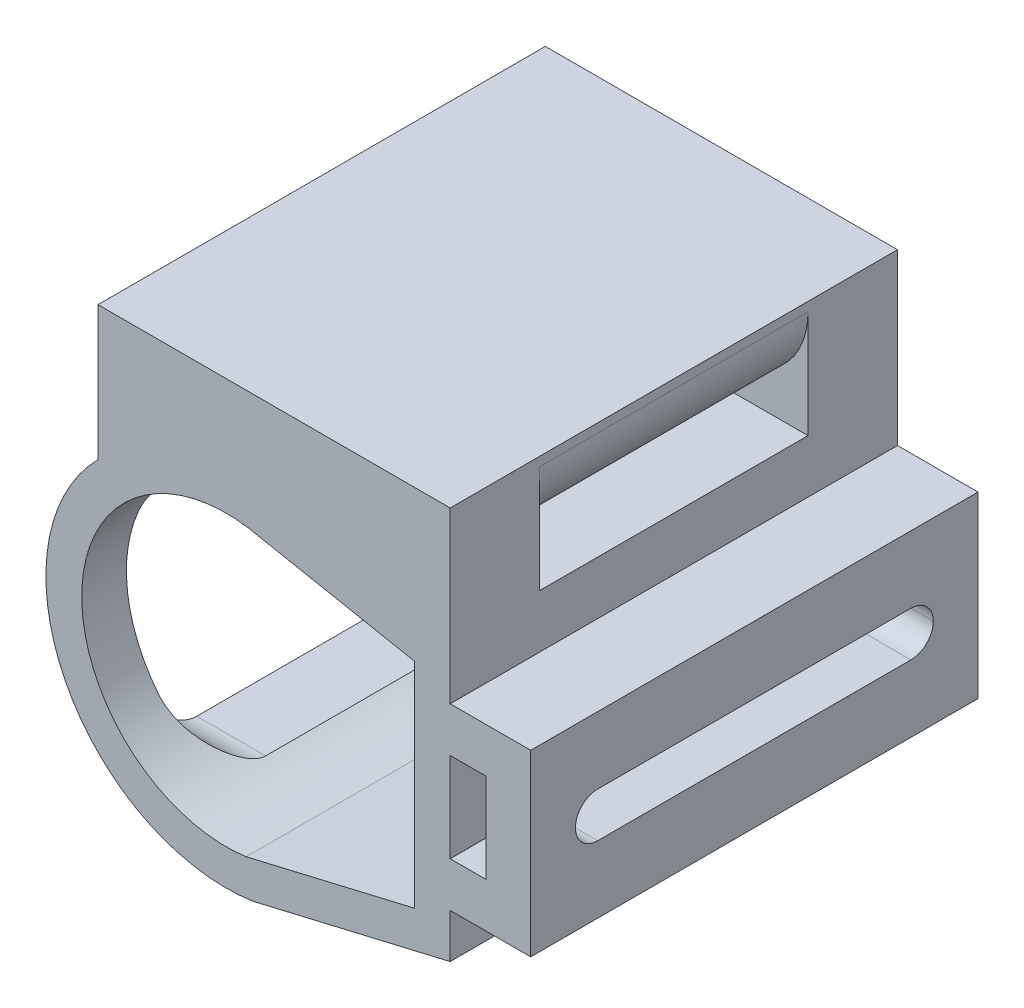
SolidWorks part; units mm, degrees
ref_plane "Alzado" through (0, 0, 0) normal (0, 0, 1) x (1, 0, 0)
ref_plane "Planta" through (0, 0, 0) normal (0, 1, 0) x (1, 0, 0)
ref_plane "Vista lateral" through (0, 0, 0) normal (1, 0, 0) x (0, 0, -1)
sketch "Croquis2" plane through (0, 0, 0) normal (0, 0, 1) x (1, 0, 0)
  line L0 (-51.9511, -1.694) -> (-49.9511, -1.694)
  line L1 (-49.9511, -1.694) -> (-51.9511, -1.694)
  line L2 (-1.9511, -10.694) -> (-1.9511, -41.694)
  line L3 (-1.9511, -41.694) -> (-51.9511, -41.694) construction
  line L4 (-51.9511, -1.694) -> (-51.9511, -41.694) construction
  line L5 (-49.9511, -1.694) -> (-49.9511, -11.294)
  line L6 (-49.9511, -11.294) -> (-36.9511, -11.294)
  line L7 (-36.9511, -11.294) -> (-36.9511, -9.294)
  line L8 (-36.9511, -9.294) -> (-31.9511, -9.294)
  line L9 (-31.9511, -9.294) -> (-31.9511, -11.994)
  line L10 (-31.9511, -11.994) -> (-17.3111, -11.994)
  line L11 (-17.3111, -11.994) -> (-17.3111, -7.694)
  line L12 (-17.3111, -7.694) -> (-24.3111, -7.694)
  line L13 (-24.3111, -7.694) -> (-24.3111, -4.694)
  line L14 (-24.3111, -4.694) -> (-14.3111, -4.694)
  line L15 (-14.3111, -4.694) -> (-14.3111, -10.694)
  line L16 (-14.3111, -10.694) -> (-1.9511, -10.694)
  line L17 (-1.9511, -41.694) -> (-4.5642, -41.694)
  line L18 (-4.5642, -41.694) -> (-4.5642, -19.454)
  line L19 (-4.5642, -19.454) -> (-22.3242, -19.454) construction
  line L20 (-22.3242, -41.694) -> (-22.3242, -15.394) construction
  line L21 (-4.5642, -19.454) -> (-22.3242, -15.394)
  line L22 (-42.1842, -30.694) -> (-40.1642, -30.694)
  line L23 (-22.3242, -15.394) -> (-26.7442, -15.394) construction
  line L24 (-42.1842, -41.694) -> (-42.1842, -30.694) construction
  line L25 (-40.1642, -41.694) -> (-40.1642, -30.694) construction
  line L26 (-26.7442, -15.394) -> (-26.7442, -15.354)
  line L27 (-22.3242, -15.394) -> (-26.7442, -15.354)
  line L28 (-40.1642, -30.694) -> (-26.7442, -15.354) construction
  arc A0 (-40.1642, -30.694) -> (-26.7442, -15.354) centre (-26.4173, -29.1801) cw
  dimension "D1" = 2
  dimension "D2" = 50
  dimension "D3" = 40
  dimension "D4" = 9.6
  dimension "D5" = 13
  dimension "D6" = 2
  dimension "D7" = 5
  dimension "D8" = 2.7
  dimension "D9" = 14.64
  dimension "D10" = 4.3
  dimension "D11" = 3
  dimension "D12" = 10
  dimension "D13" = 6
  dimension "D14" = 12.36
  dimension "D15" = 22.24
  dimension "D16" = 17.76
  dimension "D17" = 26.3
  dimension "D18" = 35.6
  dimension "D19" = 2.02
  dimension "D20" = 11
  dimension "D21" = 4.42
  dimension "D22" = 0.04
sketch "Croquis3" plane through (0, 0, 0) normal (0, 0, 1) x (1, 0, 0)
  line L218 (-8.1572, 2.8211) -> (-26.7313, 6.4418)
  line L219 (-8.1572, 2.8211) -> (-8.1572, -21.0951)
  line L220 (-8.1572, -21.0951) -> (-26.9615, -25.5138)
  line L238 (-4.1572, -24.2641) -> (-26.2158, -29.4475)
  line L239 (-4.1572, 6.1166) -> (-4.1572, -24.2641) construction
  line L250 (-43.5211, 4.6515) -> (-43.5211, 19.6515)
  line L251 (-43.5211, 19.6515) -> (-4.1572, 19.6515)
  line L253 (-4.1572, -24.2641) -> (-4.1572, 19.6515)
  line L277 (-4.1572, 6.1166) -> (-26.0389, 10.3821) construction
  arc A14 (-26.9615, -25.5138) -> (-26.7313, 6.4418) centre (-29.1957, -9.5191) cw
  arc A17 (-26.2158, -29.4475) -> (-43.5211, 4.6515) centre (-29.1957, -9.5191) cw
  arc A21 (-26.2158, -29.4475) -> (-26.0389, 10.3821) centre (-29.1957, -9.5191) cw construction
  dimension "D18" = 18.8042
  dimension "D15" = 18.574
  dimension "D3" = 15
  dimension "D29" = 16.15
  dimension "D9" = 4
  dimension "D21" = 23.9161
extrude "Saliente-Extruir1" add sketch "Croquis3" along normal blind 50 contours L238 A17 L250 L251 L253 | A14 L218 L219 L220
sketch "Croquis11" plane through (0, 0, 0) normal (0, 0, -1) x (-1, 0, 0)
  line L1 (0.1572, -9.3063) -> (-4.8428, -9.3063) construction
  line L2 (-4.8428, -19.3063) -> (-4.8428, 0.6937)
  line L3 (-4.8428, 0.6937) -> (4.1572, 0.6937)
  line L4 (4.1572, 0.6937) -> (4.1572, -4.3063)
  line L5 (4.1572, -4.3063) -> (0.1572, -4.3063)
  line L6 (0.1572, -4.3063) -> (0.1572, -14.3063)
  line L10 (4.1572, -9.3063) -> (2.5695, -9.3063) construction
  line L12 (-4.8428, -19.3063) -> (4.1572, -19.3063)
  line L13 (4.1572, -19.3063) -> (4.1572, -14.3063)
  line L14 (4.1572, -14.3063) -> (0.1572, -14.3063)
  dimension "D1" = 9
  dimension "D2" = 5
  dimension "D3" = 5
  dimension "D5" = 4
extrude "Saliente-Extruir2" add sketch "Croquis11" along direction (0, 0, -1) on the side against the normal up to surface (50 mm away) contours L13 L14 L6 L5 L4 L3 L2 L12 up to face at (-22.1265, -9.3032, 50)
sketch "Croquis12" plane through (4.8428, 0, 0) normal (1, 0, 0) x (0, 0, -1)
  line L1 (-50, 0.6937) -> (-50, -19.3063) construction
  line L2 (0, -19.3063) -> (0, 0.6937) construction
  line L3 (0, -19.3063) -> (0, 0.6937) construction
  line L5 (-45, -11.8063) -> (-5, -11.8063)
  line L8 (-5, -6.8063) -> (-45, -6.8063)
  line L9 (-45, -6.8063) -> (-45, -11.8063)
  line L11 (-5, -11.8063) -> (-5, -6.8063)
  point P2 (0, -9.3063)
  point P4 (-5, -9.3063)
  dimension "D1" = 5
  dimension "D2" = 5
  dimension "D3" = 5
extrude "Cortar-Extruir12" cut sketch "Croquis12" against normal up to surface (13 mm away) contours L11 L8 L9 L5 up to face at (-8.1572, -9.137, 25)
fillet "Redondeo1" radius 2.5 8 edges at (2.3428, -6.8063, 5) (2.3428, -6.8063, 45) (-6.1572, -11.8063, 5) (-6.1572, -6.8063, 5) (-6.1572, -11.8063, 45) (-6.1572, -6.8063, 45) (2.3428, -11.8063, 5) (2.3428, -11.8063, 45)
ref_plane "Plano1" through (-48.1572, 0, 0) normal (-1, 0, 0) x (0, 0, 1)
sketch "Croquis16" plane through (-48.1572, 0, 0) normal (-1, 0, 0) x (0, 0, 1)
  line L13 (5, 2.0572) -> (5, -24.6691)
  line L16 (0, 4.6515) -> (0, -29.6691) construction
  line L18 (50, -29.6691) -> (50, 4.6515) construction
  line L19 (5, 2.0572) -> (45, 2.0572)
  line L20 (5, 2.0572) -> (5, -24.6691)
  line L21 (5, -24.6691) -> (45, -24.6691)
  line L22 (45, 2.0572) -> (45, -24.6691)
  line L24 (0, -29.6691) -> (50, -29.6691) construction
  point P0 (25, 5.245)
  point P10 (24.9007, -25.4691)
  dimension "D3" = 5
  dimension "D4" = 26.7262
  dimension "D5" = 5
  dimension "D6" = 5
extrude "Cortar-Extruir17" cut sketch "Croquis16" against normal mid plane 40 contours L22 L19 L13 L21 region at (-48.1572, -11.306, 25)
fillet "Redondeo2" radius 5 4 edges at (-38.6357, -24.6691, 5) (-38.6357, -24.6691, 45) (-43.0727, 2.0572, 45) (-43.0727, 2.0572, 5)
sketch "Croquis21" plane through (-43.5211, 0, 0) normal (-1, 0, 0) x (0, 0, 1)
  line L0 (25, 4.6515) -> (25, 6.6515) construction
  line L1 (10, 9.6515) -> (40, 9.6515)
  line L2 (10, 9.6515) -> (10, 6.6515)
  line L3 (10, 6.6515) -> (40, 6.6515)
  line L4 (40, 9.6515) -> (40, 6.6515)
  line L5 (50, 4.6515) -> (0, 4.6515) construction
  point P8 (25, 6.6515)
  dimension "D1" = 3
  dimension "D2" = 30
  dimension "D3" = 2
extrude "Cortar-Extruir18" cut sketch "Croquis21" against normal up to next
fillet "Redondeo3" radius 9 2 edges at (-4.1572, 9.6515, 25) (-43.5211, 9.6515, 25)
